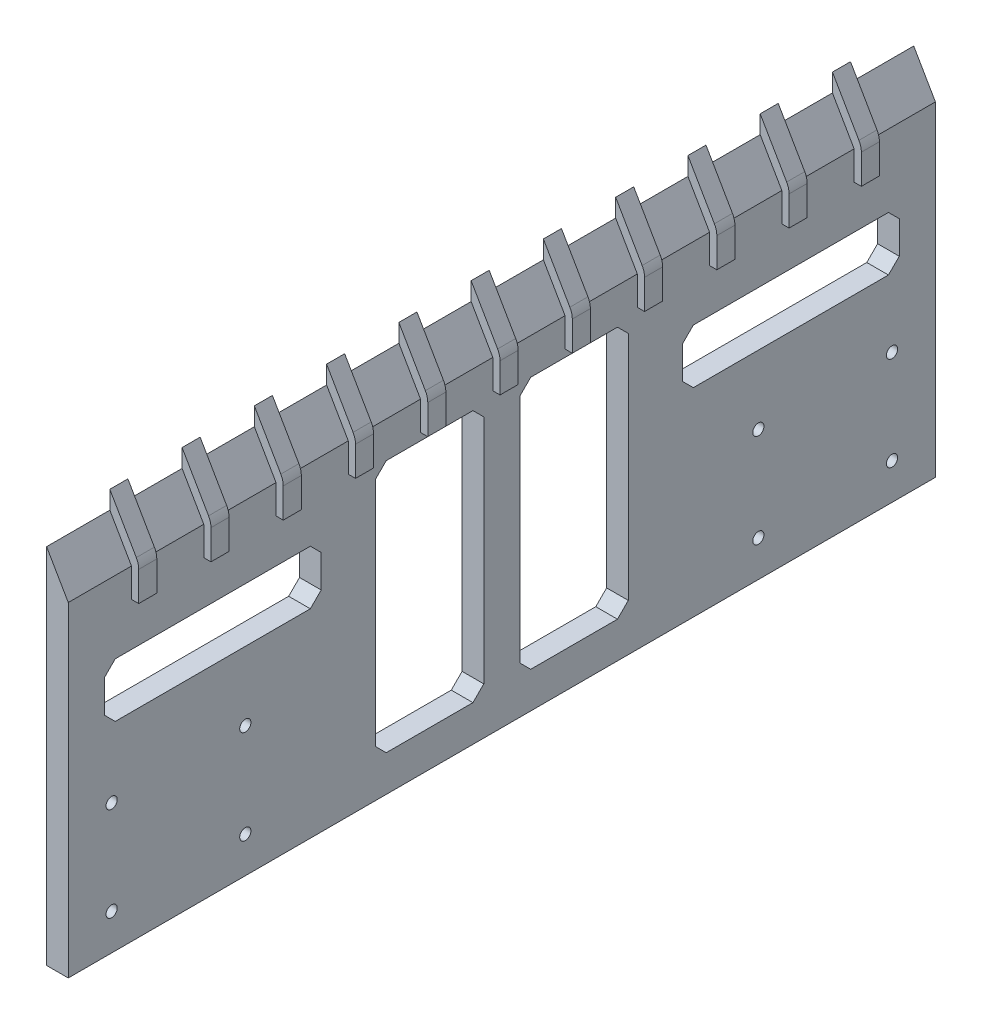
SolidWorks part; units mm, degrees
ref_plane "前视基准面" through (0, 0, 0) normal (0, 0, 1) x (1, 0, 0)
ref_plane "上视基准面" through (0, 0, 0) normal (0, 1, 0) x (1, 0, 0)
ref_plane "右视基准面" through (0, 0, 0) normal (1, 0, 0) x (0, 0, -1)
sketch "草图1" plane through (0, 0, 0) normal (1, 0, 0) x (0, 0, -1)
  line L1 (0, 0) -> (240, 0)
  line L2 (0, 0) -> (0, -90)
  line L3 (0, -90) -> (240, -90)
  line L4 (240, 0) -> (240, -90)
  dimension "D1" = 240
  dimension "D2" = 90
extrude "凸台-拉伸1" add sketch "草图1" along normal blind 6
sketch "草图2" plane through (6, 0, 0) normal (1, 0, 0) x (0, 0, -1)
  line L0 (0, 0) -> (0, -90) construction
  line L1 (12, -54) -> (49, -54) construction
  line L2 (12, -54) -> (12, -80) construction
  line L3 (12, -80) -> (49, -80) construction
  line L4 (49, -54) -> (49, -80) construction
  line L5 (240, 0) -> (0, 0) construction
  line L6 (120, 0) -> (120, -90) construction
  line L7 (0, -90) -> (240, -90) construction
  line L8 (191, -54) -> (191, -80) construction
  line L9 (228, -80) -> (191, -80) construction
  line L10 (228, -54) -> (228, -80) construction
  line L11 (228, -54) -> (191, -54) construction
  circle A0 centre (12, -54) radius 1.55
  circle A1 centre (49, -80) radius 1.55
  circle A2 centre (49, -54) radius 1.55
  circle A3 centre (12, -80) radius 1.55
  circle A4 centre (228, -80) radius 1.55
  circle A5 centre (191, -54) radius 1.55
  circle A6 centre (191, -80) radius 1.55
  circle A7 centre (228, -54) radius 1.55
  dimension "D5" = 3.1
  dimension "D1" = 12
  dimension "D2" = 54
  dimension "D3" = 37
  dimension "D4" = 26
extrude "切除-拉伸1" cut sketch "草图2" against normal through all
sketch "草图3" plane through (6, 0, 0) normal (1, 0, 0) x (0, 0, -1)
  line L0 (120, 0) -> (120, -90) construction
  line L1 (10, -20) -> (70, -20)
  line L2 (10, -20) -> (10, -35)
  line L3 (10, -35) -> (70, -35)
  line L4 (70, -20) -> (70, -35)
  line L5 (240, 0) -> (0, 0) construction
  line L6 (0, -90) -> (240, -90) construction
  line L7 (0, 0) -> (0, -90) construction
  line L8 (170, -20) -> (170, -35)
  line L9 (230, -35) -> (170, -35)
  line L10 (230, -20) -> (230, -35)
  line L11 (230, -20) -> (170, -20)
  dimension "D1" = 10
  dimension "D2" = 20
  dimension "D3" = 15
  dimension "D4" = 60
extrude "切除-拉伸2" cut sketch "草图3" against normal through all
sketch "草图4" plane through (6, 0, 0) normal (1, 0, 0) x (0, 0, -1)
  line L0 (120, 0) -> (120, -90) construction
  line L1 (85, -10) -> (115, -10)
  line L2 (85, -10) -> (85, -80)
  line L3 (85, -80) -> (115, -80)
  line L4 (115, -10) -> (115, -80)
  line L5 (240, 0) -> (0, 0) construction
  line L6 (0, -90) -> (240, -90) construction
  line L7 (0, 0) -> (0, -90) construction
  line L8 (125, -10) -> (125, -80)
  line L9 (155, -80) -> (125, -80)
  line L10 (155, -10) -> (155, -80)
  line L11 (155, -10) -> (125, -10)
  dimension "D1" = 10
  dimension "D2" = 10
  dimension "D3" = 85
  dimension "D4" = 30
extrude "切除-拉伸3" cut sketch "草图4" against normal through all contours L4 L1 L2 L3 | L8 L9 L10 L11 region at (6, -45, -100)
sketch "草图5" plane through (0, 0, 0) normal (-1, 0, 0) x (0, 0, 1)
  circle A0 centre (-191, -80) radius 3
  circle A1 centre (-228, -80) radius 3
  circle A2 centre (-191, -54) radius 3
  circle A3 centre (-228, -54) radius 3
  circle A4 centre (-45, -80) radius 3
  circle A5 centre (-12, -80) radius 3
  circle A6 centre (-12, -54) radius 3
  circle A7 centre (-49, -54) radius 3
  dimension "D1" = 6
extrude "切除-拉伸4" cut sketch "草图5" against normal blind 3
sketch "草图6" plane through (0, 0, 0) normal (0, 0, 1) x (1, 0, 0)
  line L0 (6, 0) -> (0, 0)
  line L1 (0, 0) -> (0, 10.3923)
  line L2 (0, 10.3923) -> (6, 0)
  dimension "D1" = 30
extrude "凸台-拉伸2" add sketch "草图6" against normal blind 240
ref_plane "基准面1" through (0, 0, -117.5) normal (0, 0, 1) x (1, 0, 0)
sketch "草图7" plane through (0, 0, -117.5) normal (0, 0, 1) x (1, 0, 0)
  line L0 (0, 10.3923) -> (0, 15.3923)
  line L1 (0, 15.3923) -> (8, 1.5359)
  line L2 (8, 1.5359) -> (8, -8)
  line L3 (8, -8) -> (6, -8)
  line L4 (6, 0) -> (6, -90) construction
  line L5 (6, -8) -> (6, 0)
  line L6 (6, 0) -> (0, 10.3923)
  dimension "D1" = 5
  dimension "D2" = 2
  dimension "D3" = 8
extrude "凸台-拉伸3" add sketch "草图7" against normal blind 5
pattern_linear "阵列(线性)5" count 6 spacing 20 along (0, 0, 1) count 6 spacing 20 along (0, 0, -1) of "凸台-拉伸3"
fillet "圆角5" radius 5 11 edges at (8, 1.5359, -20) (8, 1.5359, -40) (8, 1.5359, -60) (8, 1.5359, -80) (8, 1.5359, -100) (8, 1.5359, -120) (8, 1.5359, -140) (8, 1.5359, -160) (8, 1.5359, -180) (8, 1.5359, -200) (8, 1.5359, -220)
chamfer "倒角1" distance 3 angle 45 16 edges at (3, -80, -85) (3, -80, -125) (3, -35, -170) (3, -35, -230) (3, -80, -155) (3, -80, -115) (3, -20, -230) (3, -10, -155) (3, -10, -115) (3, -20, -170) (3, -10, -125) (3, -10, -85) (3, -35, -70) (3, -20, -70) (3, -35, -10) (3, -20, -10)
